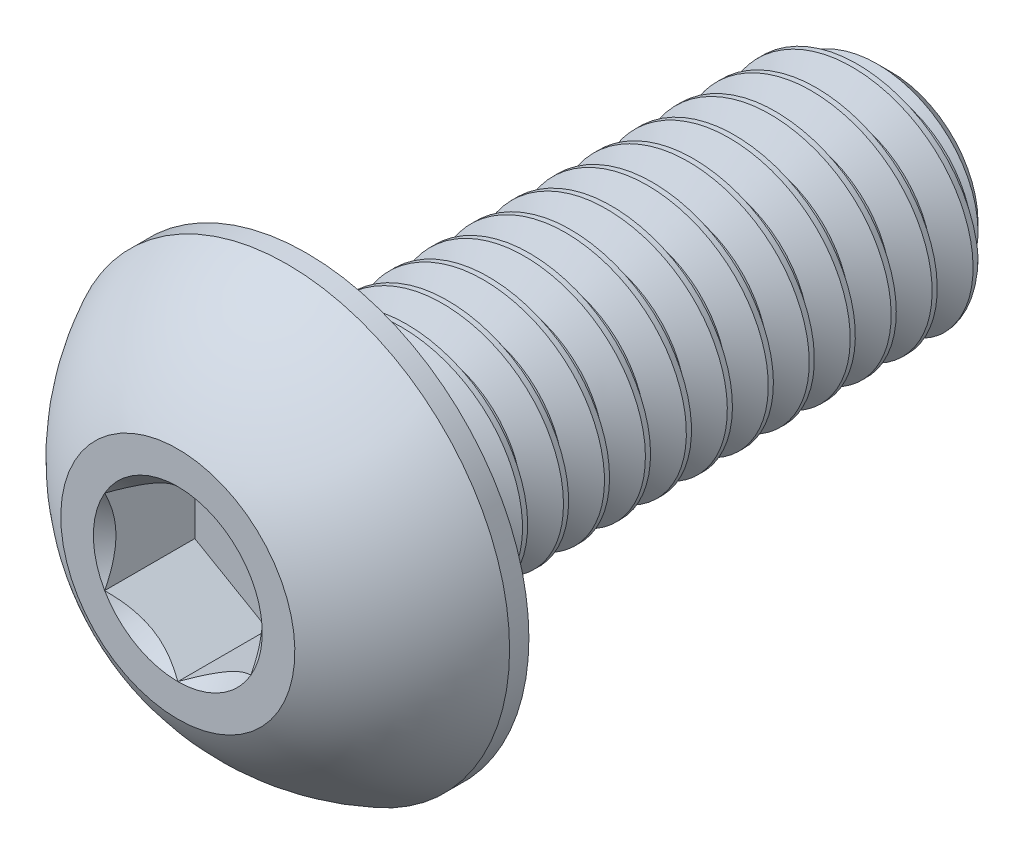
SolidWorks part; units mm, degrees
ref_plane "Front" through (0, 0, 0) normal (0, 0, 1) x (1, 0, 0)
ref_plane "Top" through (0, 0, 0) normal (0, 1, 0) x (1, 0, 0)
ref_plane "Right" through (0, 0, 0) normal (1, 0, 0) x (0, 0, -1)
sketch "Sketch1" plane through (0, 0, 0) normal (1, 0, 0) x (0, 0, -1)
  line L2 (2.2, 2) -> (12.2, 2)
  line L3 (12.2, 2) -> (12.2, 0)
  line L4 (12.2, 0) -> (2.2, 0)
  line L6 (1.87, 3.8) -> (2.2, 3.8) construction
  line L7 (12.2, 2) -> (12.2, -2) construction
  line L8 (0, 0) -> (2.2, 0) construction
  line L9 (2.2, 3.8) -> (2.2, -3.8) construction
  line L11 (2.2, 2) -> (2.2, 0)
  line L13 (0, 1.25) -> (0, -1.25) construction
  line L14 (0, 1.25) -> (0, 2) construction
  line L15 (12.1562, 2.0758) -> (12.5062, 1.4696) construction
  line L16 (12.5062, 1.4696) -> (12.8562, 2.0758) construction
  line L17 (12.8562, 2.0758) -> (12.1562, 2.0758) construction
  line L18 (12.2, 2) -> (12.8125, 2) construction
  line L19 (12.5062, 2.0758) -> (12.5062, 2) construction
  line L20 (12.5062, 2) -> (12.5062, 1.5453) construction
  line L21 (12.5062, 1.5453) -> (12.5062, 1.4696) construction
  line L22 (12.4625, 1.5453) -> (12.55, 1.5453)
  line L23 (12.1781, 2.0379) -> (12.8344, 2.0379)
  line L24 (12.55, 1.5453) -> (12.8344, 2.0379)
  line L25 (12.4625, 1.5453) -> (12.1781, 2.0379)
  line L26 (11.675, 2) -> (12.2, 1.475)
  arc A3 (0, 2) -> (1.87, 3.8) centre (3.7264, 0) cw construction
  point P29 (12.5062, 2.0379)
  point P30 (10.45, -2)
  dimension "D1" = 0.33
  dimension "Pitch" = 0.7
  dimension "D3" = 0.0875
  dimension "D2" = 0.525
  dimension "D4" = 45
  dimension "D5" = 1.75
sketch "Sketch10" plane through (0, 0, 0) normal (1, 0, 0) x (0, 0, -1)
  line L0 (11.675, 2) -> (12.2, 1.475) construction
  line L1 (11.675, 2) -> (12.2, 1.475)
  line L4 (12.2, 2) -> (2.2, 2)
  line L5 (12.2, 0) -> (12.2, 2)
  line L6 (2.2, 0) -> (12.2, 0)
  line L7 (2.2, 2) -> (2.2, 0)
  line L8 (11.675, 2) -> (2.2, 2)
  line L9 (12.2, 0) -> (12.2, 1.475)
  line L10 (2.2, 0) -> (12.2, 0)
  line L11 (2.2, 2) -> (2.2, 0)
  dimension "D1" = 0
revolve "Revolve3" add sketch "Sketch10" angle 360 about L8
sketch "Sketch7" plane through (0, 0, 0) normal (1, 0, 0) x (0, 0, -1)
  line L6 (1.87, 3.8) -> (2.2, 3.8) construction
  line L8 (0, 0) -> (2.2, 0) construction
  line L11 (2.2, 3.8) -> (2.2, -3.8) construction
  line L12 (1.87, 3.8) -> (2.2, 3.8)
  line L13 (0, 0) -> (2.2, 0)
  line L14 (0, 1.25) -> (0, -1.25) construction
  line L15 (2.2, 3.8) -> (2.2, 0)
  line L16 (0, 2) -> (0, 0)
  arc A2 (1.87, 3.8) -> (0, 2) centre (3.7264, 0) ccw construction
  arc A3 (1.87, 3.8) -> (0, 2) centre (3.7264, 0) ccw
revolve "Revolve2" add sketch "Sketch7" angle 360 mid plane about L13
sketch "Sketch5" plane through (0, 0, 0) normal (0, 0, 1) x (1, 0, 0)
  line L1 (1.25, -0.7217) -> (1.25, 0.7217)
  line L2 (1.25, 0.7217) -> (0, 1.4434)
  line L3 (0, 1.4434) -> (-1.25, 0.7217)
  line L4 (-1.25, 0.7217) -> (-1.25, -0.7217)
  line L5 (-1.25, -0.7217) -> (0, -1.4434)
  line L6 (0, -1.4434) -> (1.25, -0.7217)
  circle A0 centre (0, 0) radius 1.25 construction
extrude "Cut-Extrude2" cut sketch "Sketch5" against normal blind 1.54
sketch "Sketch6" plane through (0, 0, 0) normal (0, 0, 1) x (1, 0, 0)
  circle A0 centre (0, 0) radius 1.4434
extrude "Cut-Extrude3" cut sketch "Sketch6" against normal blind 1.54 draft 45
sketch "Sketch9" plane through (0, 0, -2.2) normal (0, 0, -1) x (-1, 0, 0)
  circle A0 centre (0, 0) radius 2 construction
  circle A4 centre (0, 0) radius 2
split "Split1" bodies to split 113 resulting bodies 123 124 split by face at (3.8, 0, -2.2)
sketch "Sketch11" plane through (0, 0, -12.2) normal (0, 0, -1) x (-1, 0, 0)
  circle A0 centre (0, 0) radius 2 construction
  circle A1 centre (0, 0) radius 2
curve "Helix/Spiral1" pitch 0.7 height 12.2 radius 2 centre (0, 0, -12.2) axis (0, 0, 1) start towards (0, 1, 0)
sketch "Sketch12" plane through (0, 0, 0) normal (1, 0, 0) x (0, 0, -1)
  line L0 (12.4625, 1.5453) -> (12.55, 1.5453) construction
  line L1 (12.55, 1.5453) -> (12.8344, 2.0379) construction
  line L2 (12.1781, 2.0379) -> (12.8344, 2.0379) construction
  line L3 (12.4625, 1.5453) -> (12.1781, 2.0379) construction
  line L4 (12.4625, 1.5453) -> (12.55, 1.5453)
  line L5 (12.55, 1.5453) -> (12.8344, 2.0379)
  line L6 (12.1781, 2.0379) -> (12.8344, 2.0379)
  line L7 (12.4625, 1.5453) -> (12.1781, 2.0379)
sweep "Cut-Sweep2" cut profiles "Sketch12" path "Helix/Spiral1" align with end faces yes
extrude "Boss-Extrude1" add sketch "Sketch9" along normal blind 10 draft 45
equation "\"D1@Cut-Extrude2\" = \"Head Ht@Sketch1\" * .7"
equation "\"D1@Sketch1\" = \"Head Ht@Sketch1\" * .15"
equation "\"D1@Cut-Extrude3\" = \"D1@Cut-Extrude2\""
equation "\"D3@Sketch1\" = \"Pitch@Sketch1\" / 8"
equation "\"D2@Sketch1\"=\"Pitch@Sketch1\"*0.75"
equation "\"D3@Helix/Spiral1\" = \"Lg@Sketch1\" + \"Head Ht@Sketch1\""
equation "\"D4@Helix/Spiral1\"=\"pitch@sketch1\""
equation "\"D5@Sketch1\"=\"Pitch@Sketch1\"*2.5"
